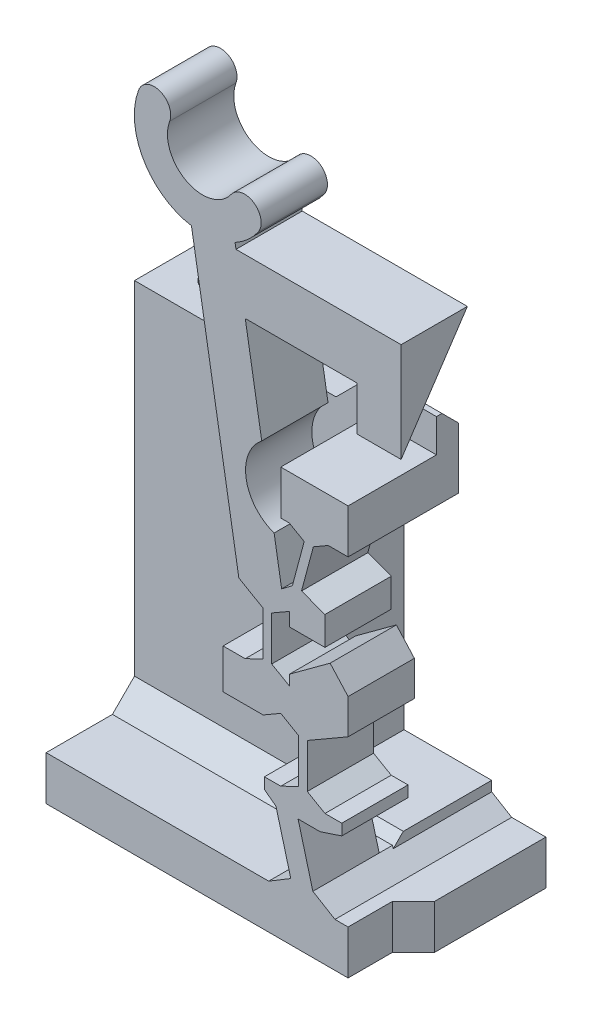
SolidWorks part; units mm, degrees
material "Nylon 6/12"
ref_plane "Front Plane" through (0, 0, 0) normal (0, 0, 1) x (1, 0, 0)
ref_plane "Top Plane" through (0, 0, 0) normal (0, 1, 0) x (1, 0, 0)
ref_plane "Right Plane" through (0, 0, 0) normal (1, 0, 0) x (0, 0, -1)
sketch "Sketch-SkeletonConfigUp" plane through (0, 0, 0) normal (0, 0, 1) x (1, 0, 0)
  line L0 (0, 0) -> (0, -50000) construction
  line L1 (0, 0) -> (4.5811, 6.2164) construction
  line L2 (9.8143, 13.3177) -> (4.5811, 13.945) construction
  line L3 (4.5811, 13.945) -> (2.9713, 10.4094) construction
  line L4 (2.9713, 10.4094) -> (4.5811, 6.2164) construction
  line L5 (4.5811, 13.945) -> (6.2429, 19.1409) construction
  line L6 (2.9713, 10.4094) -> (0.0405, 27.8193) construction
  line L7 (4.5811, 6.2164) -> (9.8143, 13.3177) construction
  line L8 (-587.3593, -797.0242) -> (9.8143, 13.3177) construction
  dimension "D2" = 7.7221
  dimension "D3" = 8.8212
  dimension "D4" = 5.2707
  dimension "D5" = 119.553
  dimension "D6" = 3.8848
  dimension "D7" = 5.4552
  dimension "D8" = 17.6549
  dimension "D9" = 4.4914
  dimension "D10" = 6.745
  dimension "D11" = 145.964
  dimension "D12" = 143.612
sketch "Sketch-SkeletonConfigDown" plane through (0, 0, 0) normal (0, 0, 1) x (1, 0, 0)
  line L0 (0, 0) -> (0, -50000) construction
  line L1 (0, 0) -> (4.5811, 6.2164) construction
  line L2 (9.8143, 13.3177) -> (4.5811, 13.945) construction
  line L3 (4.5811, 13.945) -> (6.1909, 10.4094) construction
  line L4 (6.1909, 10.4094) -> (4.5811, 6.2164) construction
  line L5 (4.5811, 13.945) -> (1.753, 18.6098) construction
  line L6 (6.1909, 10.4094) -> (-8.8652, 19.6294) construction
  line L7 (4.5811, 6.2164) -> (9.8143, 13.3177) construction
  line L8 (-589.9357, -800.5203) -> (9.8143, 13.3177) construction
  dimension "D2" = 7.7221
  dimension "D3" = 8.8212
  dimension "D4" = 5.2707
  dimension "D5" = 119.553
  dimension "D6" = 3.8848
  dimension "D7" = 5.4552
  dimension "D8" = 17.6549
  dimension "D9" = 4.4914
  dimension "D10" = 6.745
  dimension "D11" = 145.964
  dimension "D1" = 143.612
ref_plane "Plane-Cam Base" through (9.128, 0, 0) normal (1, 0, 0) x (0, 0, -1)
ref_plane "Plane-Down-to-Up Derailleur Clearance" through (6.628, 0, 0) normal (1, 0, 0) x (0, 0, -1)
ref_plane "Plane-Cam Cavity Roof" through (5.128, 0, 0) normal (1, 0, 0) x (0, 0, -1)
sketch "Sketch-SwitchBossUp" plane through (0, 0, 0) normal (0, 0, 1) x (1, 0, 0)
  line L0 (3.5811, 11.4759) -> (3.5811, 12.945) construction
  line L5 (5.5811, 12.5552) -> (5.5811, 11.263)
  line L7 (1.5115, 25.1048) -> (1.5536, 24.8548)
  line L8 (-0.4607, 24.7728) -> (1.6831, 12.0377)
  line L9 (2.9713, 10.4094) -> (0.0405, 27.8193) construction
  line L11 (0.1364, 21.2256) -> (2.1086, 21.5576) construction
  line L15 (6.628, -23.7286) -> (6.628, 23.7286) construction
  line L16 (2.9713, 10.4094) -> (4.5811, 6.2164) construction
  line L17 (3.5811, 12.945) -> (3.5811, 14.945) construction
  line L18 (5.5811, 12.945) -> (5.5811, 14.945) construction
  line L19 (4.3811, 13.945) -> (4.7811, 13.945) construction
  line L20 (3.5811, 14.945) -> (5.5811, 14.945) construction
  line L21 (3.5811, 12.945) -> (5.5811, 12.945) construction
  line L22 (4.5811, 12.945) -> (4.5811, 14.945) construction
  line L23 (4.5811, 6.2164) -> (8.5405, 7.1023) construction
  line L24 (1.9713, 9.4094) -> (1.9713, 11.4094) construction
  line L25 (3.9713, 9.4094) -> (3.9713, 11.4094) construction
  line L26 (3.9713, 9.4094) -> (1.9713, 9.4094) construction
  line L27 (1.9713, 11.4094) -> (3.9713, 11.4094) construction
  line L28 (3.5811, 7.2164) -> (5.5811, 7.2164) construction
  line L29 (3.5811, 7.2164) -> (3.5811, 5.2164) construction
  line L30 (5.5811, 7.2164) -> (5.5811, 5.2164) construction
  line L31 (3.5811, 5.2164) -> (5.5811, 5.2164) construction
  line L32 (4.7811, 6.2164) -> (4.3811, 6.2164) construction
  line L40 (3.1713, 10.4094) -> (2.7713, 10.4094) construction
  line L66 (0.0405, 27.8193) -> (0.0405, 50027.8193) construction
  line L76 (5.5811, 11.263) -> (5.5811, 12.5552) construction
  line L77 (5.5811, 7.6783) -> (6.628, 8.2827)
  line L80 (5.8152, 10.763) -> (6.628, 9.8603)
  line L81 (9.128, 1033.2419) -> (9.128, 20.0586) construction
  line L85 (6.9307, 9.5241) -> (8.5405, 7.7363) construction
  line L88 (5.7256, 17.3347) -> (6.628, 17.3347)
  line L92 (3.7762, 8.3129) -> (6.9307, 9.5241) construction
  line L98 (1.9713, 9.0164) -> (0.9713, 9.0164)
  line L99 (0.9713, 9.0164) -> (0.9713, 7.2164)
  line L100 (0.9713, 7.2164) -> (2.7811, 7.2164)
  line L101 (4.5811, 6.2164) -> (6.9307, 9.5241) construction
  line L103 (0.0405, 27.8193) -> (1.9448, 26.4638) construction
  line L104 (6.9307, 9.5241) -> (8.5405, 7.7363) construction
  line L107 (1.9713, 9.4094) -> (1.9713, 9.0164) construction
  line L109 (0.0405, 27.8193) -> (-2.1498, 28.6358) construction
  line L111 (6.628, 9.8603) -> (6.628, 8.2827)
  line L112 (6.628, 9.8603) -> (6.9307, 9.5241) construction
  line L113 (2.8424, 4.8235) -> (2.8424, 4.3235)
  line L114 (7.3693, 7.7363) -> (7.3563, 7.7363) construction
  line L121 (5.0345, -1.1719) -> (5.0345, 1.4305) construction
  line L122 (9.028, 22.3548) -> (9.028, 20.3548)
  line L127 (5.5811, 15.3347) -> (5.5811, 14.945) construction
  line L130 (6.0345, 0.8281) -> (6.628, 0.8281)
  line L132 (2.8424, 4.3235) -> (3.3646, 3.9305)
  line L133 (2.9713, 10.4094) -> (6.1909, 10.4094) construction
  line L134 (4.5811, 10.4094) -> (4.5811, 13.945) construction
  line L135 (4.5811, 10.4094) -> (4.5811, 6.2164) construction
  line L137 (3.9713, 9.4094) -> (5.5811, 7.2164) construction
  line L139 (5.8152, 10.763) -> (3.9713, 9.4094)
  line L141 (4.0345, 1.4305) -> (3.0345, 0.8281)
  line L142 (3.0345, 0.8281) -> (3.0345, -1.1719)
  line L143 (9.128, 20.0586) -> (9.128, 18.3333) construction
  line L145 (9.128, 16.6071) -> (9.128, -49992.4167) construction
  line L147 (5.5811, 11.263) -> (5.5811, 12.5552) construction
  line L150 (3.0345, -1.1719) -> (5.0345, -1.1719)
  line L151 (3.3646, 3.9305) -> (4.3646, 3.9305) construction
  line L152 (4.642, 14.945) -> (4.1061, 12.945)
  line L153 (5.0561, 14.945) -> (4.5202, 12.945)
  line L157 (3.5811, 17.3347) -> (3.5811, 15.3347)
  line L158 (5.7311, 15.3347) -> (6.628, 15.3347)
  line L162 (3.1713, 11.4094) -> (3.1713, 9.4094)
  line L164 (2.7713, 11.4094) -> (2.7713, 9.4094)
  line L169 (4.3811, 7.2164) -> (4.3811, 5.2164)
  line L170 (4.7811, 5.2164) -> (4.7811, 7.2164)
  line L175 (4.3811, 7.2164) -> (3.5811, 7.6783)
  line L176 (4.7811, 7.2164) -> (5.5811, 7.6783)
  line L177 (5.5811, 7.2164) -> (5.5811, 7.6783) construction
  line L179 (4.3811, 5.2164) -> (3.5811, 4.8235)
  line L180 (3.5811, 5.2164) -> (3.5811, 4.8235) construction
  line L181 (3.5811, 4.8235) -> (2.8424, 4.8235)
  line L183 (4.7811, 5.2164) -> (5.5811, 4.7545)
  line L184 (5.5811, 5.2164) -> (5.5811, 4.7545) construction
  line L186 (9.128, -23.7286) -> (9.128, 23.7286) construction
  line L187 (2.7713, 9.4094) -> (1.9713, 9.0164)
  line L188 (3.1713, 9.4094) -> (3.9713, 8.9475)
  line L189 (3.1713, 11.4094) -> (3.9713, 11.8713)
  line L190 (2.7713, 11.4094) -> (1.6831, 12.0377)
  line L191 (3.9713, 11.4094) -> (3.9713, 11.8713) construction
  line L192 (3.9713, 11.8713) -> (3.9713, 11.263)
  line L193 (4.5202, 12.945) -> (5.5811, 12.5552)
  line L194 (4.1061, 12.945) -> (3.6203, 12.5779)
  line L195 (3.9713, 11.263) -> (5.5811, 11.263)
  line L196 (3.9713, 9.4094) -> (3.9713, 8.9475)
  line L197 (3.5811, 7.2164) -> (3.5811, 7.6783) construction
  line L199 (3.5811, 7.6783) -> (2.7811, 7.2164)
  line L201 (2.8424, 4.3235) -> (2.8424, 3.9305) construction
  line L202 (2.8424, 3.9305) -> (3.3646, 3.9305) construction
  line L204 (5.0345, 1.4305) -> (3.0345, 1.4305) construction
  line L205 (3.0345, 1.4305) -> (3.0345, 0.8281) construction
  line L206 (5.0345, 1.4305) -> (6.0345, 0.8281)
  line L207 (9.128, 18.3333) -> (9.128, 16.6071) construction
  line L208 (6.628, -1.1719) -> (6.628, 0.8281)
  line L209 (9.128, 20.0586) -> (9.128, 16.6071) construction
  line L211 (5.0345, 1.4305) -> (4.3646, 3.9305)
  line L212 (4.0345, 1.4305) -> (3.3646, 3.9305)
  line L214 (4.642, 14.945) -> (3.9669, 15.3347)
  line L215 (3.9669, 15.3347) -> (3.5811, 15.3347)
  line L216 (5.0561, 14.945) -> (5.7311, 15.3347)
  line L217 (5.5811, 12.945) -> (5.5811, 12.5552) construction
  line L218 (5.0561, 14.945) -> (5.0561, 15.3347) construction
  line L219 (5.7311, 15.3347) -> (3.9669, 15.3347) construction
  line L221 (9.028, 22.3548) -> (9.028, 24.8548)
  line L224 (3.5811, 17.3347) -> (5.7256, 17.3347)
  line L232 (6.628, 15.3347) -> (6.628, 17.3347)
  line L233 (6.628, -1.1719) -> (5.0345, -1.1719)
  line L236 (1.5536, 24.8548) -> (9.028, 24.8548)
  line L240 (4.3646, 3.9305) -> (5.3646, 3.9305)
  line L241 (5.3646, 3.9305) -> (6.3424, 4.2545)
  line L248 (7.028, 22.3548) -> (1.9744, 22.3548)
  line L249 (1.9744, 22.3548) -> (2.7198, 17.9273)
  line L250 (9.028, 20.3548) -> (7.028, 20.3548)
  line L251 (7.028, 20.3548) -> (7.028, 22.3548)
  line L252 (3.2801, 14.5986) -> (3.6203, 12.5779)
  line L253 (4.3879, 13.9967) -> (4.7743, 13.8932) construction
  line L367 (5.5811, 4.7545) -> (6.3424, 4.7545)
  line L368 (6.3424, 4.7545) -> (6.3424, 4.2545)
  arc A0 (1.5115, 25.1048) -> (2.5558, 26.0289) centre (0.0405, 27.8193) ccw
  arc A1 (-0.4607, 24.7728) -> (-2.8525, 28.8978) centre (0.0405, 27.8193) cw
  arc A2 (-2.8525, 28.8978) -> (-1.447, 28.3738) centre (-2.1498, 28.6358) cw
  arc A3 (2.5558, 26.0289) -> (1.3338, 26.8987) centre (1.9448, 26.4638) ccw
  arc A4 (-1.447, 28.3738) -> (1.3338, 26.8987) centre (0.0405, 27.8193) ccw
  arc A5 (3.5811, 12.945) -> (3.5811, 14.945) centre (3.3561, 13.945) ccw construction
  arc A6 (5.5811, 12.945) -> (5.5811, 14.945) centre (5.8061, 13.945) cw construction
  arc A7 (2.6223, 9.8772) -> (1.9713, 11.4094) centre (1.7463, 10.4094) ccw construction
  arc A8 (3.9713, 11.4094) -> (3.9713, 9.4094) centre (4.1963, 10.4094) ccw construction
  arc A9 (3.5811, 7.2164) -> (3.5811, 5.2164) centre (3.3561, 6.2164) cw construction
  arc A10 (5.5811, 7.2164) -> (5.5811, 5.2164) centre (5.8061, 6.2164) ccw construction
  circle A28 centre (0.0405, 27.8193) radius 2.3375 construction
  arc A29 (1.9713, 9.4094) -> (2.6223, 9.8772) centre (1.7463, 10.4094) ccw construction
  arc A30 (3.2801, 14.5986) -> (2.7198, 17.9273) centre (3.9114, 16.4164) cw
  point P53 (4.5811, 13.945)
  point P63 (2.9713, 10.4094)
  point P80 (0, 0)
  point P83 (0, 0)
  point P93 (1.1225, 21.3916)
  dimension "D23" = 1.5875
  dimension "D24" = 0.75
  dimension "D2" = 2
  dimension "D5" = 2
  dimension "D8" = 42
  dimension "D16" = 42
  dimension "D27" = 120
  dimension "D28" = 120
  dimension "D30" = 120
  dimension "D32" = 120
  dimension "D33" = 120
  dimension "D34" = 120
  dimension "D17" = 0.5
  dimension "D21" = 2
  dimension "D22" = 1
  dimension "D38" = 2
  dimension "D39" = 0.5
  dimension "D40" = 60
  dimension "D41" = 1
  dimension "D42" = 45
  dimension "D43" = 120
  dimension "D10" = 15
  dimension "D12" = 2.5
  dimension "D13" = 1
  dimension "D19" = 1
  dimension "D25" = 15
  dimension "D26" = 120
  dimension "D35" = 120
  dimension "D20" = 3
  dimension "D48" = 2
  dimension "D82" = 1
  dimension "D83" = 3.5
  dimension "D14" = 2.5
  dimension "D15" = 0.25
  dimension "D7" = 2
  dimension "D9" = 2
  dimension "D18" = 1.8
  dimension "D29" = 0.4
extrude "Boss-Switch Body" add sketch "Sketch-SwitchBossUp" along normal blind 3
sketch "Sketch1" plane through (0, 0, 0) normal (0, 0, -1) x (-1, 0, 0)
  line L1 (-7.5811, -1.1719) -> (0.4122, -1.1719)
  line L2 (-7.5811, -1.1719) -> (-7.5811, 0.8281)
  line L4 (0.4122, -1.1719) -> (0.4122, 0.8281)
  line L5 (-3.5811, 18.8347) -> (-7.5811, 18.8347)
  line L10 (-7.5811, 18.8347) -> (-7.5811, 15.3347)
  line L11 (-4.0345, 1.4305) -> (-5.0345, 1.4305)
  line L12 (-7.5811, 15.3347) -> (-3.5811, 15.3347)
  line L13 (-4.0345, 1.4305) -> (-3.0345, 0.8281)
  line L14 (-3.5811, 15.3347) -> (-3.5811, 18.8347)
  line L20 (-4.3646, 3.9305) -> (-5.0345, 1.4305) construction
  line L22 (-3.0345, -1.1719) -> (-6.628, -1.1719) construction
  line L23 (-3.0345, 0.8281) -> (0.4122, 0.8281)
  line L24 (-5.0345, 1.4305) -> (-6.0345, 0.8281)
  line L25 (-6.0345, 0.8281) -> (-7.5811, 0.8281)
  dimension "D1" = 3.5
extrude "Boss-Flange Width" add sketch "Sketch1" along normal blind 5
ref_plane "Plane-Sta2Sit Groove" through (0.0405, 0, 0) normal (1, 0, 0) x (0, 0, -1)
ref_plane "Plane-Cam Outer Surface" through (-12.0395, 0, 0) normal (1, 0, 0) x (0, 0, -1)
ref_plane "Plane-FlangeTop" through (-7.0395, 0, 0) normal (1, 0, 0) x (0, 0, -1)
sketch "Sketch2" plane through (-7.0395, 0, 0) normal (1, 0, 0) x (0, 0, -1)
  line L0 (5, 15.3347) -> (-3, 15.3347) construction
  line L1 (5, 17.3347) -> (1, 17.3347)
  line L2 (5, 17.3347) -> (5, 15.3347)
  line L3 (5, 15.3347) -> (1, 15.3347)
  line L4 (1, 17.3347) -> (1, 15.3347)
  line L5 (-3, -1.1719) -> (-3, 0.8281) construction
  line L11 (5, 0.8281) -> (-3, 0.8281)
  line L12 (5, 0.8281) -> (5, -1.1719)
  line L13 (5, -1.1719) -> (-3, -1.1719)
  line L14 (-3, 0.8281) -> (-3, -1.1719)
  line L15 (0, 10.4094) -> (0, 27.8193) construction
  line L17 (5, 0.8281) -> (5, -1.1719) construction
  line L18 (-3, 0.8281) -> (0, 0.8281) construction
  dimension "D1" = 1
  dimension "D2" = 2
extrude "Boss-Flange Height" add sketch "Sketch2" along normal up to surface (11.6675 mm away)
sketch "Sketch10" plane through (0, 15.3347, 0) normal (0, 1, 0) x (1, 0, 0)
  line L0 (9.128, -23.7286) -> (9.128, 23.7286) construction
  line L1 (7.5811, 5) -> (5.128, 5)
  line L2 (7.5811, 5) -> (7.5811, 2)
  line L3 (7.5811, 2) -> (5.128, 2)
  line L5 (4.628, 7) -> (4.628, 1) construction
  line L6 (3.5811, 1) -> (-7.0395, 1) construction
  line L8 (5.128, 5) -> (5.128, 2)
  dimension "D1" = 1
  dimension "D2" = 0.5
  dimension "D3" = 4.5
extrude "Cut-Up-To-Down Derailleur Clearance" cut sketch "Sketch10" along normal up to next (3.5 mm away)
sketch "Sketch17" plane through (0, 15.3347, 0) normal (0, -1, 0) x (1, 0, 0)
  line L0 (5.128, -5) -> (-7.0395, -5)
  line L1 (5.128, -5) -> (-7.0395, -5) construction
  line L2 (-7.0395, -5) -> (-7.0395, -1)
  line L3 (-7.0395, -1) -> (5.128, -1)
  line L4 (5.128, -1) -> (5.128, -5)
  line L5 (-7.0395, -1) -> (-7.0395, -5) construction
extrude "Boss-Flange Support" add sketch "Sketch17" along normal up to surface (14.5065 mm away) up to face at (-2.0025, 0.8281, -1)
sketch "Sketch-HolePositions" plane through (0, -1.1719, 0) normal (0, -1, 0) x (1, 0, 0)
  line L0 (-7.0395, -3) -> (7.5811, -3) construction
  line L1 (7.5811, -5) -> (-7.0395, -5) construction
  line L2 (7.5811, -5) -> (7.5811, 0) construction
  line L4 (-7.0395, -22.2167) -> (-7.0395, 22.2167) construction
  point P6 (-5.0395, -3)
  point P7 (-0.5395, -3)
  dimension "D1" = 2
  dimension "D2" = 4.5
  dimension "D3" = 2
sketch "Sketch6" plane through (0, -1.1719, 0) normal (0, -1, 0) x (-1, 0, 0)
  point P0 (5.0395, 3)
  point P3 (0.5395, 3)
hole_wizard "Tap Drill for M2x0.4 Tap1" positions "Sketch6" profile "Sketch5" hole size "M2x0.4" standard "ANSI Metric" end condition through all
sketch "Sketch5" plane through (-5.0395, -1.1719, -3) normal (1, 0, 0) x (0, 0, -1)
  line L0 (0, 0) -> (0, 30.5577)
  line L1 (0, 30.5577) -> (0.8, 30.5577)
  line L2 (0.8, 30.5577) -> (0.8, 0)
  line L5 (0.8, 0) -> (0, 0)
  line L11 (0, -6.35) -> (0, 107.95) construction
  dimension "Thru Hole Dia." = 1.6
  dimension "Thru Hole Depth" = 30.5577
sketch "Sketch9" plane through (0, -1.1719, 0) normal (0, -1, 0) x (1, 0, 0)
  point P0 (-5.0395, -3)
  point P3 (-0.5395, -3)
hole_wizard "M2 Clearance Hole2" positions "Sketch9" profile "Sketch8" hole size "M2" standard "ANSI Metric"
sketch "Sketch8" plane through (-5.0395, -1.1719, -3) normal (1, 0, 0) x (0, 0, -1)
  line L0 (0, 0) -> (0, 15.721)
  line L1 (0, 15.721) -> (1.2, 15)
  line L2 (1.2, 15) -> (1.2, 0)
  line L5 (1.2, 0) -> (0, 0)
  line L10 (0, 15.721) -> (-1.2, 15) construction
  line L11 (0, -6.35) -> (0, 107.95) construction
  dimension "Hole Dia." = 2.4
  dimension "Hole Depth" = 15
  dimension "Drill Angle" = 118
sketch "Sketch-Measurements for Derailleur Ramps" [suppressed] plane through (0, 0, 0) normal (0, 0, 1) x (1, 0, 0)
  line L0 (3.184, 15.1695) -> (2.4687, 19.4188)
  line L1 (2.8264, 17.2941) -> (1.8402, 17.1281)
  line L2 (2.9713, 10.4094) -> (0.0405, 27.8193) construction
  line L3 (1.8402, 17.1281) -> (-1.3081, 15.0016)
  line L4 (6.1909, 10.4094) -> (-8.8652, 19.6294) construction
  line L5 (1.8402, 17.1281) -> (2.6012, 12.6077)
  line L6 (2.6012, 12.6077) -> (-1.3081, 15.0016)
  line L7 (0.2661, 16.0649) -> (0.2661, 17.1281)
  line L8 (0.2661, 17.1281) -> (1.8402, 17.1281)
  line L9 (6.1909, 10.4094) -> (2.9713, 10.4094)
  line L10 (5.386, 8.3129) -> (3.7762, 8.3129)
  line L11 (2.6116, 18.5698) -> (1.5115, 25.1048) construction
  line L12 (6.1909, 10.4094) -> (4.5811, 6.2164) construction
  line L13 (4.5811, 8.3129) -> (4.5811, 8.7912)
  line L14 (4.5811, 6.2164) -> (5.386, 8.3129)
  line L15 (2.9713, 10.4094) -> (4.5811, 6.2164) construction
  line L16 (3.7762, 8.3129) -> (4.5811, 6.2164)
  line L17 (5.386, 8.3129) -> (5.386, 8.7912)
  dimension "D1" = 1.5742
  dimension "D2" = 0.8049
ref_plane "Plane1" through (0, 7.1023, 0) normal (0, 1, 0) x (1, 0, 0)
ref_plane "Plane-Cantilever Cut" [suppressed] through (7.0848, 8.5204, -1.9058) normal (-0.6301, -0.7578, 0.1695) x (-0.7765, 0.6151, -0.1368)
sketch "Sketch14" [suppressed] plane through (7.0848, 8.5204, -1.9058) normal (-0.6301, -0.7578, 0.1695) x (-0.7765, 0.6151, -0.1368)
  line L0 (2.3023, -1.6911) -> (-0.3551, -1.6911)
  line L2 (2.3023, -4.3362) -> (2.3023, -1.6911)
  line L3 (-0.3551, -1.6911) -> (-0.3551, -4.4608)
  line L5 (-0.3551, -4.4608) -> (1.0087, -5.0843)
  line L6 (1.0087, -5.0843) -> (2.3023, -4.3362)
extrude "Cut-Down-to-Up Cantilever Slope" [suppressed] cut sketch "Sketch14" against normal up to next
ref_plane "Plane-Symmetry Plane" through (0, 0, 1.5) normal (0, 0, 1) x (1, 0, 0)
sketch "Sketch-Cable Center Point" plane through (0, 0, 1.5) normal (0, 0, 1) x (1, 0, 0)
  line L0 (0.0405, 27.8193) -> (0.1722, 27.0366)
  line L1 (2.9713, 10.4094) -> (0.0405, 27.8193) construction
  point P0 (0.0405, 27.8193)
  dimension "D1" = 0.7937
chamfer "Chamfer-Flange Support" distance 1.5 angle 45 1 edges at (3.5811, 17.3347, -3)
chamfer "Chamfer-Flange Support 2" distance 1.5 angle 45 2 edges at (5.128, 17.0847, -2) (5.128, 15.3347, -1.5)
chamfer "Chamfer-Flange Support 3" distance 1 angle 45 1 edges at (-2.0025, 0.8281, -1)
chamfer "Chamfer7" [suppressed] distance 1 angle 45
sketch "Sketch23" plane through (0, 0, -1) normal (0, 0, 1) x (1, 0, 0)
  line L0 (5.128, 1.8281) -> (1.1605, 1.8281)
  line L1 (-7.0395, 1.8281) -> (5.128, 1.8281) construction
  line L2 (1.1605, 1.8281) -> (1.1605, 13.8347)
  line L3 (1.1605, 13.8347) -> (5.128, 13.8347)
  line L4 (5.128, 13.8347) -> (5.128, 1.8281)
  line L5 (0.6605, -1.1719) -> (0.6605, 13.8281) construction
  dimension "D1" = 0.5
extrude "Cut-Gap for Printing" cut sketch "Sketch23" against normal through all
sketch "Sketch25" plane through (0, 0, 0) normal (0, 0, 1) x (1, 0, 0)
  line L0 (6.628, 15.3347) -> (7.5811, 15.3347)
  line L1 (7.5811, 15.3347) -> (7.5811, 18.8347)
  line L2 (7.5811, 18.8347) -> (6.628, 18.8347)
  line L3 (6.628, -23.7286) -> (6.628, 23.7286) construction
  line L4 (7.5811, 18.8347) -> (3.5811, 18.8347) construction
  line L5 (6.628, 18.8347) -> (6.628, 15.3347)
  line L6 (7.5811, 18.8347) -> (7.5811, 15.3347) construction
extrude "Cut-Derailleur Clearance" cut sketch "Sketch25" against normal through all
chamfer "Chamfer8" distance 1 angle 45 1 edges at (6.628, -0.1719, 0)
ref_plane "Plane2" through (-3.0866, 5.589, 8.3835) normal (0.2929, -0.5304, -0.7956) x (-0.9561, -0.1625, -0.2437)
sketch "Sketch26" plane through (-3.0866, 5.589, 8.3835) normal (0.2929, -0.5304, -0.7956) x (-0.9561, -0.1625, -0.2437)
  line L0 (-7.553, 20.6804) -> (-7.553, 14.9094)
  line L1 (-12.6703, 20.6804) -> (-5.5238, 20.6804) construction
  line L3 (-7.553, 14.9094) -> (-20.0302, 14.9094)
  line L4 (-20.0302, 14.9094) -> (-20.0302, 20.6804)
  line L5 (-20.0302, 20.6804) -> (-7.553, 20.6804)
extrude "Cut-Up-to-Down Cantilever Slope" cut sketch "Sketch26" along normal up to next
sketch "Sketch27" plane through (5.128, 0, 0) normal (1, 0, 0) x (0, 0, -1)
  line L0 (3.5, 18.8347) -> (3.5, 13.8347) construction
  line L1 (2.5, 18.8347) -> (5, 18.8347)
  line L2 (2.5, 18.8347) -> (2.5, 13.8347)
  line L3 (2.5, 13.8347) -> (5, 13.8347)
  line L4 (5, 18.8347) -> (5, 13.8347)
  dimension "D1" = 1
extrude "Cut-Wide Derailleur Clearance" cut sketch "Sketch27" against normal blind 4 and the other way through all
chamfer "Chamfer9" distance 1.25 angle 45 1 edges at (4.8545, 18.8347, -2.5)
sketch "Sketch28" plane through (0, 0, -1) normal (0, 0, 1) x (1, 0, 0)
  line L0 (3.5811, 18.8347) -> (6.628, 18.8347)
  line L1 (6.628, 18.8347) -> (6.628, 17.3347)
  line L2 (6.628, 17.3347) -> (3.5811, 17.3347)
  line L3 (3.5811, 17.3347) -> (3.5811, 18.8347)
extrude "Cut-Extrude1" cut sketch "Sketch28" along normal up to surface (1 mm away) up to face at (5.1045, 18.0847, 0)
equation "\"axle-diameter\"=2"
equation "\"switch-thickness\"=12"
equation "\"base-width\"=4.0"
equation "\"axle-bushing-radius\"=3"
equation "\"clearance\"= 0.25"
equation "\"arm-width\"=1.5"
equation "\"min-diameter\"=70"
equation "\"alpha\"=143.6120"
equation "\"gamma\"=119.5526"
equation "\"delta\"=145.9637"
equation "\"epsilon\"=6.7452"
equation "\"l_AB\"=8.8212"
equation "\"l_AC\"=4.4914"
equation "\"l_BD\"=5.2707"
equation "\"l_CD\"=3.8848"
equation "\"l_CE\"=17.6549"
equation "\"l_DF\"=5.4552"
equation "\"l_OA\"=7.7221"
equation "\"D2@Sketch-SkeletonConfigUp\" = \"l_OA\""
equation "\"D3@Sketch-SkeletonConfigUp\" = \"l_AB\""
equation "\"D4@Sketch-SkeletonConfigUp\" = \"l_BD\""
equation "\"D5@Sketch-SkeletonConfigUp\" = \"gamma\""
equation "\"D6@Sketch-SkeletonConfigUp\" = \"l_CD\""
equation "\"D7@Sketch-SkeletonConfigUp\" = \"l_DF\""
equation "\"D8@Sketch-SkeletonConfigUp\" = \"l_CE\""
equation "\"D9@Sketch-SkeletonConfigUp\" = \"l_AC\""
equation "\"D_groove\"=3.175"
equation "\"D7@Sketch-SkeletonConfigDown\" = \"l_DF\""
equation "\"D6@Sketch-SkeletonConfigDown\" = \"l_CD\""
equation "\"D2@Sketch-SkeletonConfigDown\" = \"l_OA\""
equation "\"D3@Sketch-SkeletonConfigDown\" = \"l_AB\""
equation "\"D9@Sketch-SkeletonConfigDown\" = \"l_AC\""
equation "\"D8@Sketch-SkeletonConfigDown\" = \"l_CE\""
equation "\"D5@Sketch-SkeletonConfigDown\" = \"gamma\""
equation "\"D4@Sketch-SkeletonConfigDown\" = \"l_BD\""
equation "\"D1@Sketch-SkeletonConfigDown\" = \"alpha\""
equation "\"hinge_length\"=1.5"
equation "\"hinge_depth\"=0.25"
equation "\"D10@Sketch-SkeletonConfigUp\"=\"epsilon\""
equation "\"D11@Sketch-SkeletonConfigUp\"=\"delta\""
equation "\"D12@Sketch-SkeletonConfigUp\"=\"alpha\""
equation "\"D11@Sketch-SkeletonConfigDown\"=\"delta\""
equation "\"D10@Sketch-SkeletonConfigDown\"=\"epsilon\""
equation "\"EE_dx\"=8.9056"
equation "\"EE_dy\"=8.1898"
equation "\"r_groove\"=\"D_groove\"/2"
equation "\"t_wall\"=25.4/16"
equation "\"width_lower\"=\"D_groove\"+\"t_wall\""
equation "\"cable_to_bottom\"=30.6257"
equation "\"switch_EE-up_base_dy\"=24"
equation "\"switch_EE-down_base_dy\"=16"
equation "\"D_axle\"=25.4/8"
equation "\"D_up_to_down\"=16"
equation "\"D_down_to_up\"=25"
equation "\"t_cam_base\"=7.5"
equation "\"D23@Sketch-SwitchBossUp\"=\"D_groove\"/2"
equation "\"D1@Sketch-Cable Center Point\"=\"D_groove\"/4"
